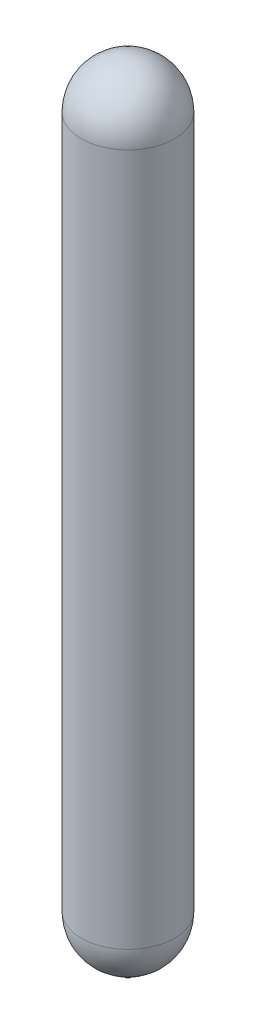
SolidWorks part; units mm, degrees
note: The reader was unsure of these and kept them because the rebuilt part matched: shared geometry of "Sketch1<4>".
ref_plane "Front Plane" through (0, 0, 0) normal (0, 0, 1) x (1, 0, 0)
ref_plane "Top Plane" through (0, 0, 0) normal (0, 1, 0) x (1, 0, 0)
ref_plane "Right Plane" through (0, 0, 0) normal (1, 0, 0) x (0, 0, -1)
sketch "Sketch1"
  line L0 (-117.0432, 2112.0202) -> (-117.0432, 0)
  line L1 (-138.8872, 2112.0202) -> (-138.8872, 0)
  line L2 (-142.2146, 0) -> (-142.2146, 2112.0202)
  line L3 (0, 50.358) -> (0, -222.3667) construction
  line L6 (0, 2254.2348) -> (0, 2250.9074)
  line L7 (0, 2229.0634) -> (0, 2250.9074)
  line L9 (-3.175, -167.0464) -> (-12.7, -167.0464)
  line L10 (-12.7, -167.0464) -> (-12.7, -138.3053)
  line L11 (-3.175, -117.0001) -> (-3.175, -167.0464)
  arc A0 (-117.0432, 2112.0202) -> (0, 2229.0634) centre (0, 2112.0202) cw
  arc A1 (-138.8872, 2112.0202) -> (0, 2250.9074) centre (0, 2112.0202) cw
  arc A2 (-142.2146, 2112.0202) -> (0, 2254.2348) centre (0, 2112.0202) cw
  arc A3 (-117.0432, 0) -> (-3.175, -117.0001) centre (0, 0) ccw
  arc A4 (-138.8872, 0) -> (-12.7, -138.3053) centre (0, 0) ccw
  arc A5 (-142.2146, 0) -> (-12.7, -141.6464) centre (0, 0) ccw
  point P14 (-3.175, -132.8732)
  point P18 (0, 0)
  point P21 (0, 0)
  dimension "D5" = 142.2146
  dimension "D4" = 2112.0202
  dimension "D1" = 142.2146
  dimension "D2" = 3.3274
  dimension "D3" = 21.844
  dimension "D7" = 9.525
  dimension "D8" = 25.4
  dimension "D6" = 15.873
  dimension "D9" = 3.175
sketch "Sketch1<4>" plane through (0, 0, 0) normal (0, 0, 1) x (1, 0, 0) same geometry as "Sketch1"
revolve "Revolve1" add sketch "Sketch1" angle 360 about L3
revolve "Revolve2" add sketch "Sketch1<4>" angle 360 about L3
equation "\"OD\"= 5.599'outside diameter"
equation "\"D1@Sketch1\"=\"OD\""
equation "\"t_wrap\"= 0.131'carbon fiber thickness"
equation "\"D2@Sketch1\"=\"t_wrap\""
equation "\"t_wall\"= .86'aluminum thickness"
equation "\"D3@Sketch1\"=\"t_wall\""
equation "\"D5@Sketch1\"=\"OD\""
